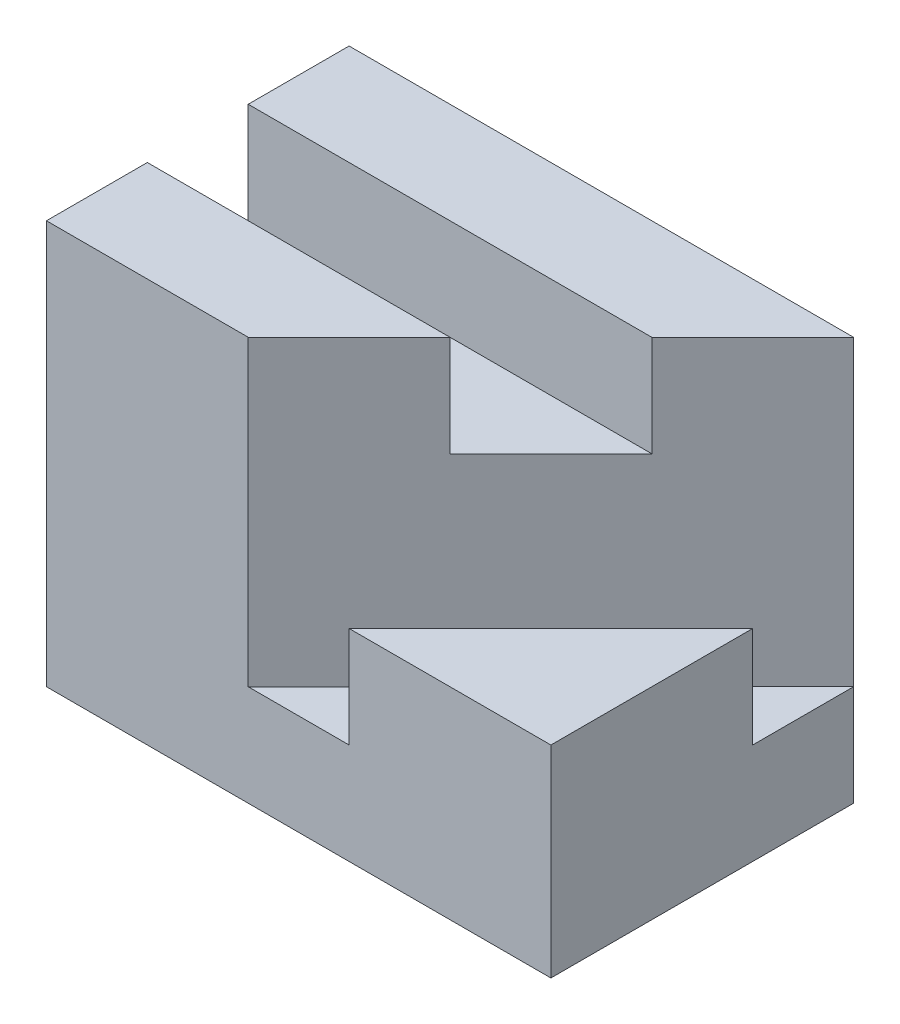
SolidWorks part; units mm, degrees
ref_plane "前基準面" through (0, 0, 0) normal (0, 0, 1) x (1, 0, 0)
ref_plane "上基準面" through (0, 0, 0) normal (0, 1, 0) x (1, 0, 0)
ref_plane "右基準面" through (0, 0, 0) normal (1, 0, 0) x (0, 0, -1)
sketch "草圖1" plane through (0, 0, 0) normal (0, 1, 0) x (1, 0, 0)
  line L1 (2.5, 1.5) -> (-2.5, 1.5)
  line L2 (2.5, 1.5) -> (2.5, -1.5)
  line L3 (2.5, -1.5) -> (-2.5, -1.5)
  line L4 (-2.5, 1.5) -> (-2.5, -1.5)
  line L5 (2.5, 1.5) -> (-2.5, -1.5) construction
  line L6 (2.5, -1.5) -> (-2.5, 1.5) construction
  point P0 (0, 0)
  dimension "D1" = 3
  dimension "D2" = 5
extrude "填料-伸長1" add sketch "草圖1" along normal blind 4
sketch "草圖3" plane through (0, 4, 0) normal (0, 1, 0) x (1, 0, 0)
  line L0 (-2.5, 1.5) -> (-2.5, -1.5) construction
  line L1 (-2.5, -0.5) -> (0.5, -0.5)
  line L2 (-2.5, -0.5) -> (-2.5, 0.5)
  line L3 (-2.5, 0.5) -> (1.5, 0.5)
  line L5 (2.5, 1.5) -> (1.5, 0.5)
  line L6 (-2.5, -1.5) -> (2.5, -1.5) construction
  line L7 (0.5, -1.5) -> (2.5, 0.5)
  line L8 (2.5, -1.5) -> (2.5, 1.5) construction
  line L9 (2.5, 1.5) -> (-2.5, 1.5) construction
  line L10 (0.5, -0.5) -> (-0.5, -1.5)
  line L11 (-0.5, -1.5) -> (0.5, -1.5)
  line L12 (2.5, 0.5) -> (2.5, 1.5)
  line L13 (1.5, 0.5) -> (0.5, -0.5)
  line L15 (-2.5, -1.5) -> (2.5, -1.5)
  line L16 (-2.5, -1.5) -> (-2.5, 1.5)
  line L17 (-2.5, 1.5) -> (2.5, 1.5)
  line L18 (2.5, -1.5) -> (2.5, 1.5)
  line M13 (-2.5, 1.5) -> (-2.5, -1.5)
  line M14 (-2.5, -1.5) -> (2.5, -1.5)
  line M15 (2.5, -1.5) -> (2.5, 1.5)
  dimension "D1" = 1
  dimension "D2" = 1
  dimension "D3" = 3
  dimension "D5" = 2
  dimension "D6" = 1
extrude "除料-伸長1" cut sketch "草圖3" against normal blind 1 contours L13 L3 L1 M13 | L5 L13 L10 L7 M14 M15 | L7 M14 M15 region at (-0.7381, 4, -0.0238) region at (1.2333, 4, 0.2333) region at (1.8333, 4, 0.8333)
extrude "除料-伸長2" cut sketch "草圖3<3>" against normal blind 3 contours L5 L13 L10 L7 M14 M15 region at (1.2333, 4, 0.2333)
sketch "草圖3<3>" plane through (0, 4, 0) normal (0, 1, 0) x (1, 0, 0) same geometry as "草圖3"
extrude "除料-伸長3" cut sketch "草圖3<4>" against normal blind 2 contours L7 M14 M15 region at (1.8333, 4, 0.8333)
sketch "草圖3<4>" plane through (0, 4, 0) normal (0, 1, 0) x (1, 0, 0) same geometry as "草圖3"
